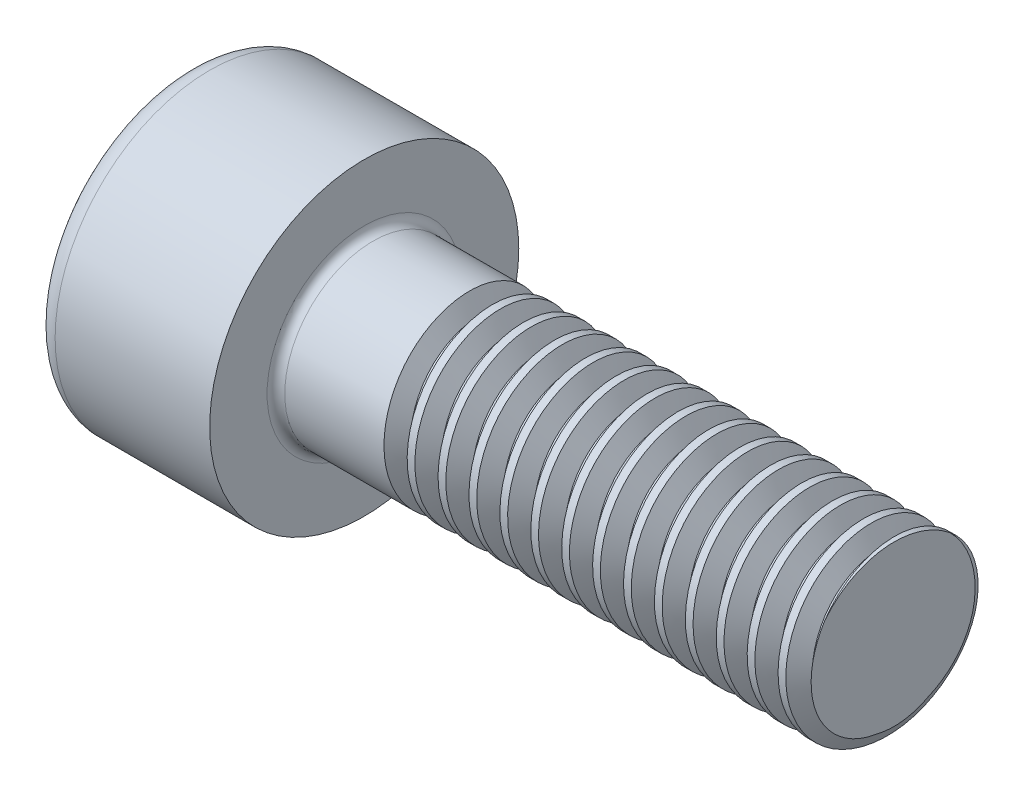
SolidWorks part; units mm, degrees
ref_plane "Спереди" through (0, 0, 0) normal (0, 0, 1) x (1, 0, 0)
ref_plane "Сверху" through (0, 0, 0) normal (0, 1, 0) x (1, 0, 0)
ref_plane "Справа" through (0, 0, 0) normal (1, 0, 0) x (0, 0, -1)
sketch "Эскиз1" plane through (0, 0, 0) normal (0, 0, 1) x (1, 0, 0)
  line L0 (22.1989, 0) -> (16, 0) construction
  line L1 (0, 16.1035) -> (0, -19.7496) construction
  line L2 (0, 0) -> (16, 0)
  line L3 (0, 0) -> (0, 3.5)
  line L4 (0, 3.5) -> (4, 3.5)
  line L5 (4, 3.5) -> (4, 2)
  line L6 (4, 2) -> (16, 2)
  line L7 (16, 2) -> (16, 0)
  dimension "D1" = 7
  dimension "D2" = 4
  dimension "D3" = 12
  dimension "D4" = 4
revolve "Повернуть1" add sketch "Эскиз1" angle 360 about L0
thread "Резьба1" pitch 0.7 method cut profile "Профиль резьбы2" start angle 0, offset 2.1, length 0, pitch 0.7, diameter 4
ref_plane "Плоскость2" through (6.1, 0, -2) normal (0, 1, 0) x (0, 0, 1)
sketch "Профиль резьбы2" plane through (6.1, 0, -2) normal (0, 1, 0) x (0, 0, 1)
  line L0 (0, 0) -> (0, 0.7) construction
  line L1 (0, 0) -> (0.3789, 0.2187)
  line L2 (0.3789, 0.2187) -> (0.3789, 0.3062)
  line L3 (0.3789, 0.3062) -> (0, 0.525)
  line L4 (0.3789, 0.2625) -> (0, 0.2625) construction
  line L11 (0, 0) -> (0, 0.525)
  point P2 (0, 0)
  dimension "Pitch" = 0.7
  dimension "Profile_Angle" = 60
  dimension "Profile_Land" = 0.0875
  dimension "Profile_Height" = 0.3789
sketch "Эскиз6" plane through (0, 0, 0) normal (-1, 0, 0) x (0, 0, 1)
  line L0 (0, 0) -> (-5.0338, 0) construction
  line L1 (0, 0) -> (0, 5.5177) construction
  line L3 (-1.72, 0) -> (-0.86, -1.4896)
  line L4 (-0.86, -1.4896) -> (0.86, -1.4896)
  line L5 (0.86, -1.4896) -> (1.72, 0)
  line L6 (1.72, 0) -> (0.86, 1.4896)
  line L7 (0.86, 1.4896) -> (-0.86, 1.4896)
  line L8 (-0.86, 1.4896) -> (-1.72, 0)
  dimension "D1" = 2.9792
  dimension "D2" = 3.44
extrude "Вырез-Вытянуть1" cut sketch "Эскиз6" against normal blind 2 contours L3 L4 L5 L6 L7 L8
extrude "Вырез-Вытянуть2" cut sketch "Эскиз6<3>" against normal blind 2 draft 60 from offset 2 offset against normal yes
sketch "Эскиз6<3>" plane through (0, 0, 0) normal (-1, 0, 0) x (0, 0, 1) same geometry as "Эскиз6"
fillet "Скругление2" radius 0.5 1 edges at (0, 0, -3.5)
fillet "Скругление3" radius 0.2 1 edges at (4, 0, -2)
